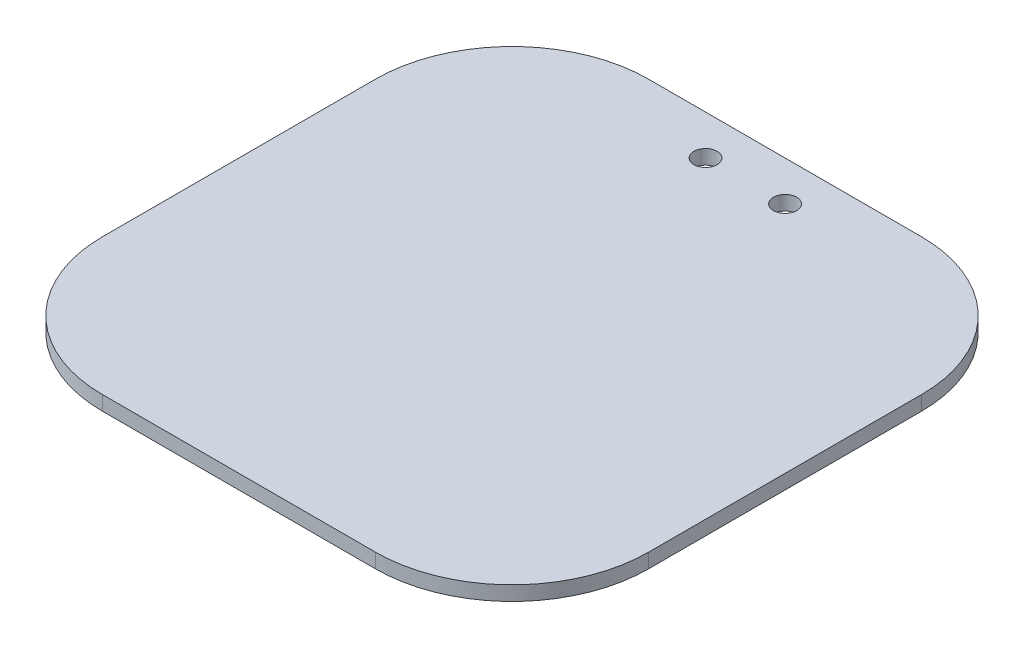
SolidWorks part; units mm, degrees
ref_plane "Front" through (0, 0, 0) normal (0, 0, 1) x (1, 0, 0)
ref_plane "Top" through (0, 0, 0) normal (0, 1, 0) x (1, 0, 0)
ref_plane "Right" through (0, 0, 0) normal (1, 0, 0) x (0, 0, -1)
sketch "Sketch1" plane through (0, 0, 0) normal (0, 1, 0) x (1, 0, 0)
  line L1 (-30, 60) -> (30, 60)
  line L2 (-60, 30) -> (-60, -30)
  line L3 (-30, -60) -> (30, -60)
  line L4 (60, 30) -> (60, -30)
  line L5 (-60, 60) -> (60, -60) construction
  line L6 (-60, -60) -> (60, 60) construction
  arc A0 (30, -60) -> (60, -30) centre (30, -30) ccw
  arc A1 (60, 30) -> (30, 60) centre (30, 30) ccw
  arc A2 (-30, 60) -> (-60, 30) centre (-30, 30) ccw
  arc A3 (-60, -30) -> (-30, -60) centre (-30, -30) ccw
  point P0 (0, 0)
  dimension "D3" = 30
  dimension "D1" = 120
  dimension "D2" = 120
extrude "Boss-Extrude1" add sketch "Sketch1" along normal blind 3.175
hole_wizard "#10 Clearance Hole1" positions "Sketch2" profile "Sketch3" hole size "#10" standard "ANSI Inch" end condition through all
sketch "Sketch2" plane through (0, 3.175, 0) normal (0, 1, 0) x (1, 0, 0)
  line L0 (-8.7376, 51.2624) -> (8.7376, 51.2624)
  line L2 (0, 0) -> (0, 51.2624)
  line L3 (30, 60) -> (-30, 60) construction
  point P0 (8.7376, 51.2624)
  point P2 (-8.7376, 51.2624)
  dimension "D1" = 8.7376
  dimension "D2" = 17.4752
sketch "Sketch3" plane through (8.7376, 3.175, -51.2624) normal (1, 0, 0) x (0, 0, 1)
  line L0 (0, 0) -> (0, 3.175)
  line L1 (0, 3.175) -> (2.5527, 3.175)
  line L2 (2.5527, 3.175) -> (2.5527, 0)
  line L5 (2.5527, 0) -> (0, 0)
  line L11 (0, -6.35) -> (0, 107.95) construction
  dimension "Thru Hole Dia." = 5.1054
  dimension "Thru Hole Depth" = 3.175
